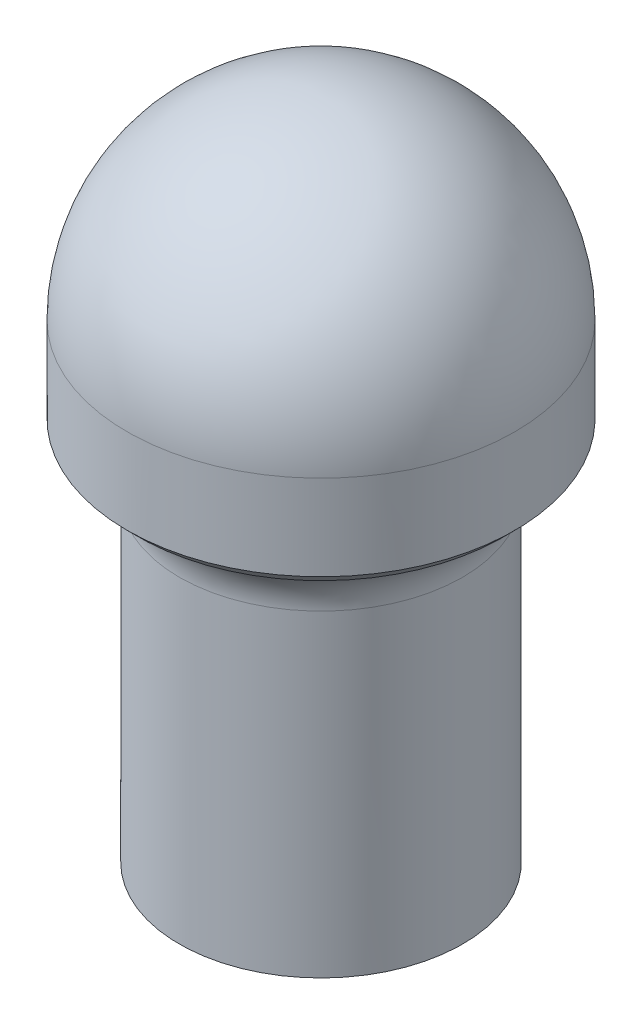
SolidWorks part; units mm, degrees
material "6061-T6 (SS)"
ref_plane "Front Plane" through (0, 0, 0) normal (0, 0, 1) x (1, 0, 0)
ref_plane "Top Plane" through (0, 0, 0) normal (0, 1, 0) x (1, 0, 0)
ref_plane "Right Plane" through (0, 0, 0) normal (1, 0, 0) x (0, 0, -1)
sketch "Sketch1" plane through (0, 0, 0) normal (0, 0, 1) x (1, 0, 0)
  line L0 (0, 25.4) -> (0, 43.6626) construction
  line L1 (3.6957, 25.4) -> (-3.6957, 25.4) construction
  line L2 (4.8966, 14.7066) -> (-5.3865, 14.7066) construction
  line L3 (-5.334, 38.3286) -> (-5.334, 35.7251)
  line L4 (-5.334, 35.7251) -> (-3.899, 35.7251)
  line L5 (-3.899, 35.7251) -> (-3.899, 25.4)
  line L6 (-3.899, 25.4) -> (0, 25.4)
  line L7 (0, 25.4) -> (0, 43.6626)
  arc A0 (0, 43.6626) -> (-5.334, 38.3286) centre (0, 38.3286) ccw
  dimension "D2" = 10.668
  dimension "D1" = 28.956
  dimension "D3" = 7.798
  dimension "D4" = 18.2626
  dimension "D5" = 7.9375
revolve "Revolve1" add sketch "Sketch1" angle 360 about L0
fillet "Fillet1" radius 1.5875 1 edges at (0, 35.7251, -3.899)
chamfer "Chamfer2" distance 0.254 angle 45 1 edges at (0, 35.7251, -5.334) first distance on face at (0, 35.7251, -5.334)
